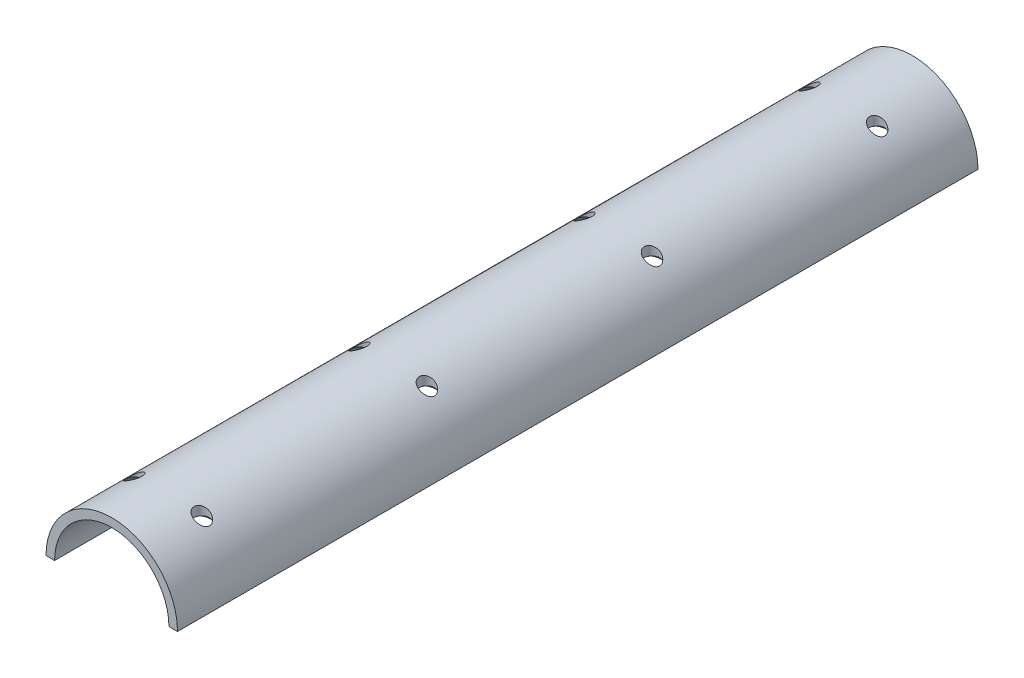
SolidWorks part; units mm, degrees
ref_plane "Front Plane" through (0, 0, 0) normal (0, 0, 1) x (1, 0, 0)
ref_plane "Top Plane" through (0, 0, 0) normal (0, 1, 0) x (1, 0, 0)
ref_plane "Right Plane" through (0, 0, 0) normal (1, 0, 0) x (0, 0, -1)
sketch "Sketch2" plane through (0, 0, 0) normal (0, 0, 1) x (1, 0, 0)
  circle A0 centre (0, 0) radius 29.21
  dimension "D1" = 58.42
extrude "Boss-Extrude1" add sketch "Sketch2" against normal blind 355.6
sketch "Sketch3" plane through (0, 0, 0) normal (0, 0, 1) x (1, 0, 0)
  circle A0 centre (0, 0) radius 25.4
  dimension "D1" = 50.8
extrude "Cut-Extrude1" cut sketch "Sketch3" against normal through all
sketch "Sketch4" plane through (0, 0, 0) normal (0, 1, 0) x (1, 0, 0)
  line L1 (-29.21, 355.6) -> (29.21, 355.6)
  line L2 (-29.21, 355.6) -> (-29.21, 0)
  line L3 (-29.21, 0) -> (29.21, 0)
  line L4 (29.21, 355.6) -> (29.21, 0)
extrude "Cut-Extrude2" cut sketch "Sketch4" against normal up to next
sketch "Sketch5" plane through (0, 0, 0) normal (0, 1, 0) x (1, 0, 0)
  line L0 (0, 319.7815) -> (0, 0) construction
  line L1 (-29.21, 0) -> (29.21, 0) construction
  point P3 (15, 25)
  point P6 (-15, 25)
  point P7 (15, 75)
  point P9 (-15, 75)
  point P10 (15, 125)
  point P11 (-15, 125)
  point P12 (15, 175)
  point P13 (-15, 175)
  point P14 (15, 225)
  point P15 (-15, 225)
  point P16 (15, 275)
  point P17 (-15, 275)
  point P18 (15, 325)
  point P19 (-15, 325)
  dimension "D1" = 25
  dimension "D2" = 15
  dimension "D4" = 50
  dimension "D3" = 7
hole_wizard "CSK for 1/4 Flat Head Machine Screw1" positions "Sketch9" profile "Sketch10" countersink size "1/4" standard "ANSI Inch" end condition through all
sketch "Sketch9" plane through (0, 0, 0) normal (0, -1, 0) x (-1, 0, 0)
  point P0 (-15, 25)
  point P6 (15, 25)
  point P13 (-15, 125)
  point P16 (15, 125)
  point P25 (-15, 225)
  point P28 (15, 225)
  point P37 (-15, 325)
  point P40 (15, 325)
  point P43 (0, 0)
  point P44 (0, 0)
  point P45 (0, 0)
sketch "Sketch10" plane through (15, 0, -25) normal (1, 0, 0) x (0, 0, -1)
  line L0 (0, 0) -> (0, 29.21)
  line L1 (0, 29.21) -> (3.3782, 29.21)
  line L2 (3.3782, 29.21) -> (3.3782, 22.5209)
  line L3 (3.3782, 22.5209) -> (6.4389, 19)
  line L4 (6.4389, 19) -> (6.4389, 0)
  line L6 (6.4389, 0) -> (0, 0)
  line L7 (-3.3782, 22.5209) -> (-6.4389, 19) construction
  line L11 (0, -6.35) -> (0, 107.95) construction
  dimension "Thru Hole Dia." = 6.7564
  dimension "Thru Hole Depth" = 29.21
  dimension "C'Sink Dia." = 12.8778
  dimension "C'Sink Angle" = 82
  dimension "Head Clearance" = 19
